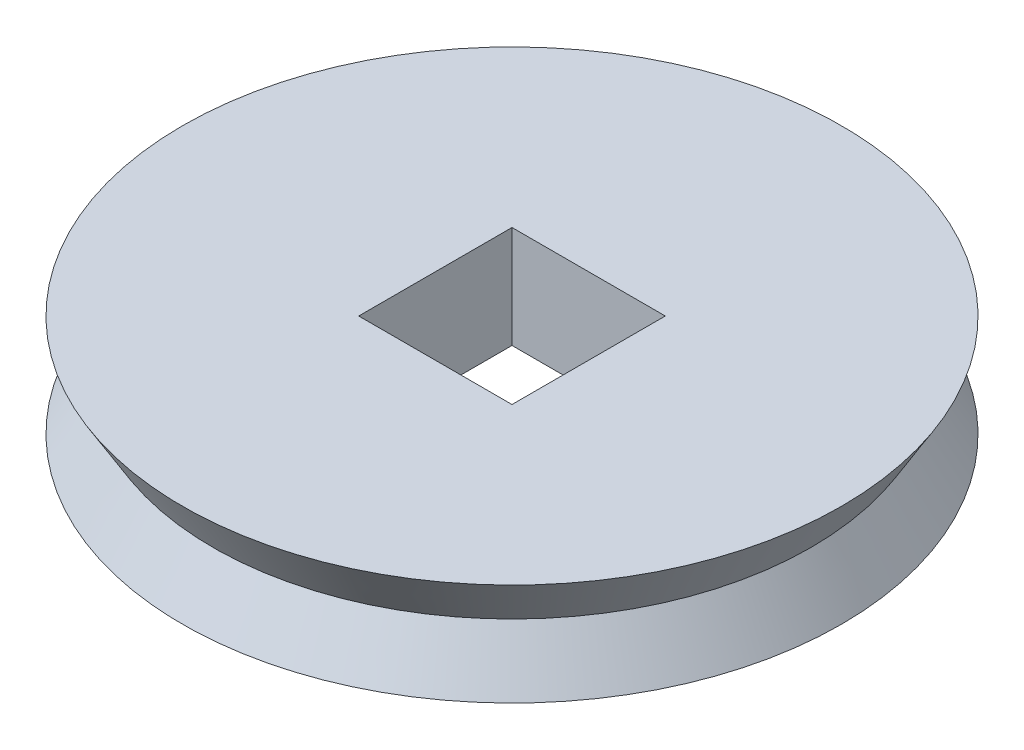
SolidWorks part; units mm, degrees
ref_plane "Front Plane" through (0, 0, 0) normal (0, 0, 1) x (1, 0, 0)
ref_plane "Top Plane" through (0, 0, 0) normal (0, 1, 0) x (1, 0, 0)
ref_plane "Right Plane" through (0, 0, 0) normal (1, 0, 0) x (0, 0, -1)
sketch "Sketch1" plane through (0, 0, 0) normal (0, 1, 0) x (1, 0, 0)
  circle A0 centre (0, 0) radius 32.25
  dimension "D1" = 64.5
extrude "Boss-Extrude1" add sketch "Sketch1" along normal blind 10
sketch "Sketch2" plane through (0, 0, 0) normal (0, 0, 1) x (1, 0, 0)
  line L0 (-32.25, 0) -> (32.25, 0) construction
  line L1 (32.25, 10) -> (-32.25, 10) construction
  line L2 (-32.25, 0) -> (32.25, 0) construction
  line L3 (32.25, 10) -> (-32.25, 10) construction
  line L4 (32.25, 10) -> (29.25, 5)
  line L5 (29.25, 5) -> (32.25, 0)
  line L6 (32.25, 0) -> (32.25, 10)
  point P4 (0, 0)
  point P6 (32.25, 5)
  dimension "D1" = 3
sweep "Cut-Sweep1" cut profiles "Sketch2" path "Sketch1<2>"
sketch "Sketch1<2>" plane through (0, 0, 0) normal (0, 1, 0) x (1, 0, 0) same geometry as "Sketch1"
sketch "Sketch3" plane through (0, 10, 0) normal (0, 1, 0) x (1, 0, 0)
  line L1 (-7.5, -7.5) -> (7.5, -7.5)
  line L2 (-7.5, -7.5) -> (-7.5, 7.5)
  line L3 (-7.5, 7.5) -> (7.5, 7.5)
  line L4 (7.5, -7.5) -> (7.5, 7.5)
  line L5 (-7.5, -7.5) -> (7.5, 7.5) construction
  line L6 (-7.5, 7.5) -> (7.5, -7.5) construction
  point P0 (0, 0)
  dimension "D1" = 15
  dimension "D2" = 15
extrude "Cut-Extrude1" cut sketch "Sketch3" against normal through all
